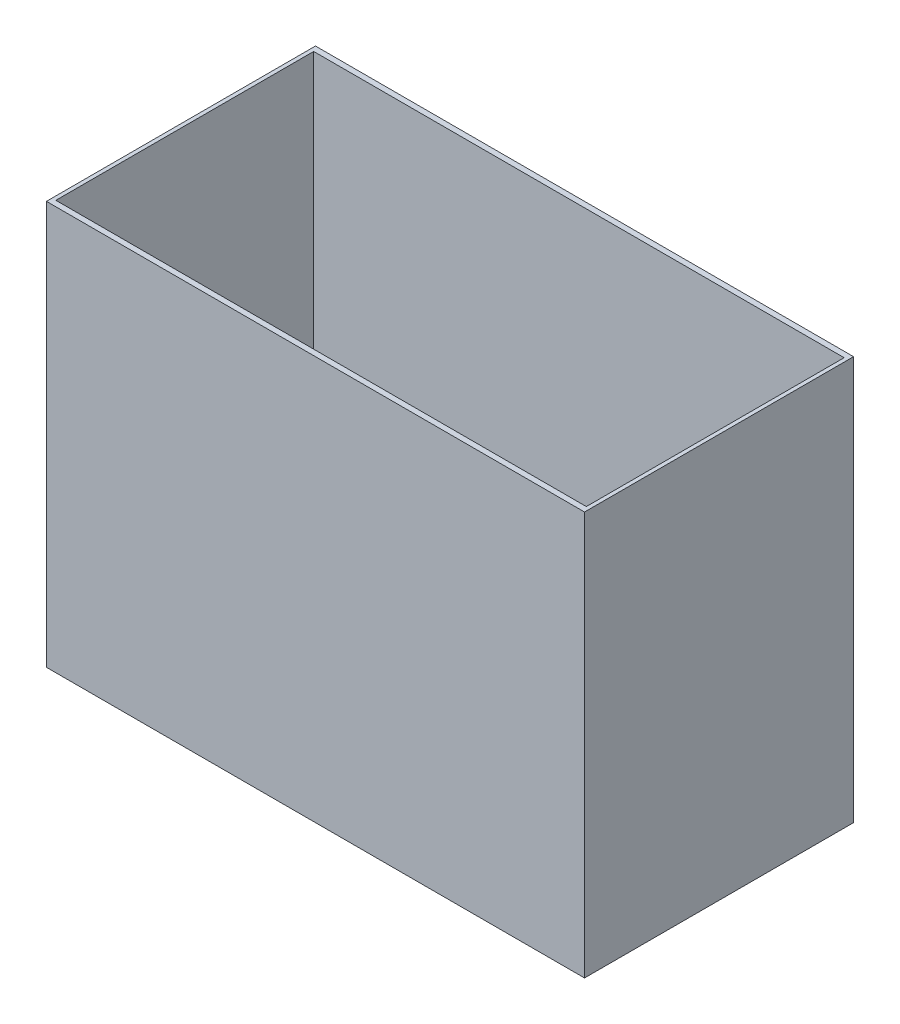
SolidWorks part; units mm, degrees
ref_plane "Front Plane" through (0, 0, 0) normal (0, 0, 1) x (1, 0, 0)
ref_plane "Top Plane" through (0, 0, 0) normal (0, 1, 0) x (1, 0, 0)
ref_plane "Right Plane" through (0, 0, 0) normal (1, 0, 0) x (0, 0, -1)
other "Bounding Box"
ref_plane "Default Plane" through (-292.1, 0, -139.7) normal (0, 1, 0) x (1, 0, 0)
sketch "Sketch1" plane through (0, 0, 0) normal (0, 1, 0) x (1, 0, 0)
  line L0 (-292.1, -139.7) -> (165.1, -139.7) construction
  line L5 (292.1, 139.7) -> (88.9, 139.7)
  line L6 (292.1, 139.7) -> (292.1, -139.7)
  line L7 (292.1, -139.7) -> (88.9, -139.7)
  line L8 (88.9, 139.7) -> (88.9, -139.7)
  dimension "D1" = 203.2
extrude "Boss-Extrude1" add sketch "Sketch1" along normal blind 6.35
sketch "Sketch2" plane through (0, 6.35, 0) normal (0, 1, 0) x (1, 0, 0)
  line L0 (-245.9259, -63.5) -> (-55.3589, -63.5) construction
  line L1 (342.9, -120.6497) -> (431.8, -120.6497)
  line L2 (342.9, -120.6497) -> (342.9, -101.5997)
  line L3 (342.9, -101.5997) -> (431.8, -101.5997)
  line L4 (431.8, -120.6497) -> (431.8, -101.5997)
  line L5 (342.9, -120.6497) -> (431.8, -101.5997) construction
  line L6 (342.9, -101.5997) -> (431.8, -120.6497) construction
  line L7 (292.1, 139.7) -> (292.1, -139.7) construction
  line L8 (292.1, 0) -> (88.9, 0) construction
  line L9 (88.9, -139.7) -> (88.9, 139.7) construction
  line L10 (190.5, 0) -> (190.5, 121.6784) construction
  line L11 (38.1, -101.5997) -> (-50.8, -120.6497) construction
  line L12 (38.1, -120.6497) -> (-50.8, -101.5997) construction
  line L13 (-50.8, -120.6497) -> (-50.8, -101.5997)
  line L14 (38.1, -101.5997) -> (-50.8, -101.5997)
  line L15 (38.1, -120.6497) -> (38.1, -101.5997)
  line L16 (38.1, -120.6497) -> (-50.8, -120.6497)
  point P0 (387.35, -111.1247)
  point P17 (-6.35, -111.1247)
  dimension "D1" = 19.05
  dimension "D2" = 88.9
  dimension "D3" = 38.0997
  dimension "D4" = 50.8
  dimension "D5" = 63.5
extrude "Boss-Extrude2" [suppressed] add sketch "Sketch2" along normal blind 304.8 separate body contours L2 L1 L4 L3
pattern_linear "LPattern1" [suppressed] count 2 spacing 304.8 of bodies 101
pattern_linear "LPattern2" [suppressed] count 2 spacing 215.9 of bodies 101
sketch "Sketch3" plane through (0, 0, 0) normal (0, 1, 0) x (1, 0, 0)
  line L1 (-304.8, -152.4) -> (304.8, -152.4)
  line L2 (-304.8, -152.4) -> (-304.8, 152.4)
  line L3 (-304.8, 152.4) -> (304.8, 152.4)
  line L4 (304.8, -152.4) -> (304.8, 152.4)
  line L5 (-304.8, -152.4) -> (304.8, 152.4) construction
  line L6 (-304.8, 152.4) -> (304.8, -152.4) construction
  line L7 (-300.482, -146.05) -> (300.482, -146.05)
  line L8 (-300.482, -146.05) -> (-300.482, 146.05)
  line L9 (-300.482, 146.05) -> (300.482, 146.05)
  line L10 (300.482, -146.05) -> (300.482, 146.05)
  line L11 (-300.482, -146.05) -> (300.482, 146.05) construction
  line L12 (-300.482, 146.05) -> (300.482, -146.05) construction
  point P0 (0, 0)
  point P6 (0, 0)
  dimension "D1" = 609.6
  dimension "D2" = 304.8
  dimension "D3" = 292.1
  dimension "D4" = 600.964
extrude "Boss-Extrude3" add sketch "Sketch3" along normal blind 457.2 separate body
sketch "Sketch4" plane through (0, 6.35, 0) normal (0, 1, 0) x (1, 0, 0)
  circle A2 centre (252.0119, 99.6119) radius 21.0381 construction
  circle A3 centre (252.0119, 99.6119) radius 21.0381
extrude "Cut-Extrude1" cut sketch "Sketch4" against normal through all
mirror "Mirror1" about plane through (0, 0, 0) normal (0, 0, 1) of "Cut-Extrude1"
sketch "Sketch5" plane through (0, 6.35, 0) normal (0, 1, 0) x (1, 0, 0)
  line L0 (292.1, 0) -> (222.2453, 0) construction
  line L1 (292.1, -139.7) -> (292.1, 139.7) construction
  line L2 (292.1, 60.96) -> (267.107, 60.96) construction
  line L3 (292.1, 43.18) -> (285.75, 43.18)
  line L4 (292.1, 43.18) -> (292.1, 17.78)
  line L5 (292.1, 17.78) -> (285.75, 17.78)
  line L6 (285.75, 43.18) -> (285.75, 17.78)
  line L7 (285.75, 78.74) -> (285.75, 104.14)
  line L8 (292.1, 104.14) -> (285.75, 104.14)
  line L9 (292.1, 78.74) -> (292.1, 104.14)
  line L10 (292.1, 78.74) -> (285.75, 78.74)
  line L12 (285.75, 104.14) -> (285.75, 139.7) construction
  line L13 (292.1, 139.7) -> (88.9, 139.7) construction
  line L14 (285.75, 43.18) -> (285.75, 78.74) construction
  line L15 (285.75, 17.78) -> (285.75, -17.78) construction
  line L16 (292.1, -78.74) -> (285.75, -78.74)
  line L17 (292.1, -78.74) -> (292.1, -104.14)
  line L18 (292.1, -104.14) -> (285.75, -104.14)
  line L19 (285.75, -78.74) -> (285.75, -104.14)
  line L20 (285.75, -43.18) -> (285.75, -17.78)
  line L21 (292.1, -17.78) -> (285.75, -17.78)
  line L22 (292.1, -43.18) -> (292.1, -17.78)
  line L23 (292.1, -43.18) -> (285.75, -43.18)
  dimension "D1" = 6.35
  dimension "D2" = 25.4
extrude "Cut-Extrude2" cut sketch "Sketch5" against normal through all
sketch "Sketch6" plane through (0, 6.35, 0) normal (0, 1, 0) x (1, 0, 0)
  circle A4 centre (133.5003, -46.1866) radius 21.0381 construction
  circle A5 centre (210.6176, 12.194) radius 21.0381 construction
  circle A6 centre (133.5003, -46.1866) radius 21.0381
  circle A7 centre (210.6176, 12.194) radius 21.0381
extrude "Cut-Extrude3" cut sketch "Sketch6" against normal through all
sketch "Sketch7" plane through (0, 6.35, 0) normal (0, 1, 0) x (1, 0, 0)
  line L4 (88.9, 0) -> (141.0565, 0)
  line L5 (88.9, 139.7) -> (88.9, -139.7) construction
  line L6 (95.377, -57.277) -> (88.773, -57.277)
  line L7 (95.377, -31.623) -> (95.377, -57.277)
  line L8 (88.773, 57.277) -> (88.773, 31.623)
  line L9 (88.773, 31.623) -> (95.377, 31.623)
  line L10 (95.377, 31.623) -> (95.377, 57.277)
  line L11 (95.377, 57.277) -> (88.773, 57.277)
  line L12 (88.773, 57.277) -> (88.773, 31.623)
  line L13 (88.773, 31.623) -> (95.377, 31.623)
  line L14 (95.377, 31.623) -> (95.377, 57.277)
  line L15 (95.377, 57.277) -> (88.773, 57.277)
  line L16 (88.773, -31.623) -> (95.377, -31.623)
  line L17 (88.773, -57.277) -> (88.773, -31.623)
  line M28 (88.9, 139.7) -> (88.9, -139.7)
  dimension "D1" = 0.127
extrude "Cut-Extrude4" cut sketch "Sketch7" against normal through all contours L14 L15 L13 M28 | L16 L6 L7 M28 region at (92.1385, 6.35, -44.45) region at (92.1385, 6.35, 44.45)
